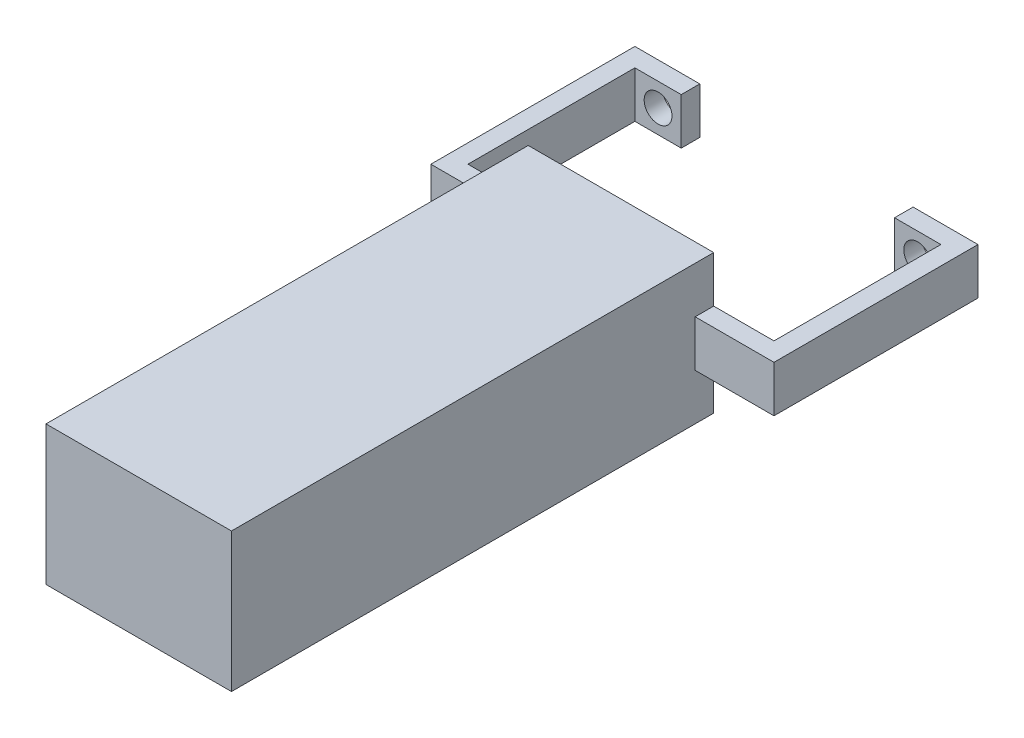
SolidWorks part; units mm, degrees
ref_plane "Спереди" through (0, 0, 0) normal (0, 0, 1) x (1, 0, 0)
ref_plane "Сверху" through (0, 0, 0) normal (0, 1, 0) x (1, 0, 0)
ref_plane "Справа" through (0, 0, 0) normal (1, 0, 0) x (0, 0, -1)
sketch "Эскиз1" plane through (0, 0, 0) normal (0, 0, 1) x (1, 0, 0)
  line L3 (11.5, 0) -> (11.5, 2.5)
  line L4 (11.5, 2.5) -> (16.5, 2.5)
  line L7 (11.5, -2.5) -> (11.5, 0)
  line L8 (11.5, -2.5) -> (16.5, -2.5)
  line L14 (-16.5, 2.5) -> (-18.5, 2.5)
  line L15 (-11.5, 0) -> (-11.5, 2.5)
  line L16 (-11.5, 2.5) -> (-16.5, 2.5)
  line L18 (-16.5, -2.5) -> (-11.5, -2.5)
  line L19 (-11.5, -2.5) -> (-11.5, 0)
  line L20 (-18.5, 2.5) -> (-18.5, -2.5)
  line L21 (-18.5, -2.5) -> (-16.5, -2.5)
  line L22 (16.5, -2.5) -> (18.5, -2.5)
  line L23 (18.5, -2.5) -> (18.5, 2.5)
  line L24 (18.5, 2.5) -> (16.5, 2.5)
  circle A0 centre (14, 0) radius 1.5
  circle A1 centre (-14, 0) radius 1.5
extrude "Бобышка-Вытянуть1" add sketch "Эскиз1" along normal blind 2
sketch "Эскиз3" plane through (0, 0, 2) normal (0, 0, 1) x (1, 0, 0)
  line L0 (-18.5, 2.5) -> (-16.5, 2.5)
  line L1 (-11.5, 2.5) -> (-18.5, 2.5) construction
  line L2 (-16.5, 2.5) -> (-16.5, -2.5)
  line L3 (-18.5, -2.5) -> (-11.5, -2.5) construction
  line L4 (-16.5, -2.5) -> (-18.5, -2.5)
  line L5 (-18.5, -2.5) -> (-18.5, 2.5)
  line L6 (18.5, -2.5) -> (16.5, -2.5)
  line L7 (11.5, -2.5) -> (18.5, -2.5) construction
  line L8 (16.5, -2.5) -> (16.5, 2.5)
  line L9 (18.5, 2.5) -> (11.5, 2.5) construction
  line L10 (16.5, 2.5) -> (18.5, 2.5)
  line L11 (18.5, 2.5) -> (18.5, -2.5)
extrude "Бобышка-Вытянуть2" add sketch "Эскиз3" along normal blind 18
sketch "Эскиз4" plane through (18.5, 0, 0) normal (1, 0, 0) x (0, 0, -1)
  line L0 (-20, -2.5) -> (-22, -2.5)
  line L1 (-22, -2.5) -> (-22, 2.5)
  line L2 (-22, 2.5) -> (-20, 2.5)
  line L3 (-20, -2.5) -> (-20, 2.5) construction
  line L4 (-20, 2.5) -> (-20, -2.5)
extrude "Бобышка-Вытянуть3" add sketch "Эскиз4" against normal blind 37
sketch "Эскиз5" plane through (0, 0, 22) normal (0, 0, 1) x (1, 0, 0)
  line L1 (-18.5, 2.5) -> (18.5, 2.5) construction
  line L2 (-10, 2.5) -> (-10, 7.5)
  line L3 (-10, 7.5) -> (10, 7.5)
  line L4 (10, 7.5) -> (10, -7.5)
  line L5 (10, -7.5) -> (-10, -7.5)
  line L6 (-10, -7.5) -> (-10, 2.5)
extrude "Бобышка-Вытянуть4" add sketch "Эскиз5" along normal blind 50 and the other way blind 2
